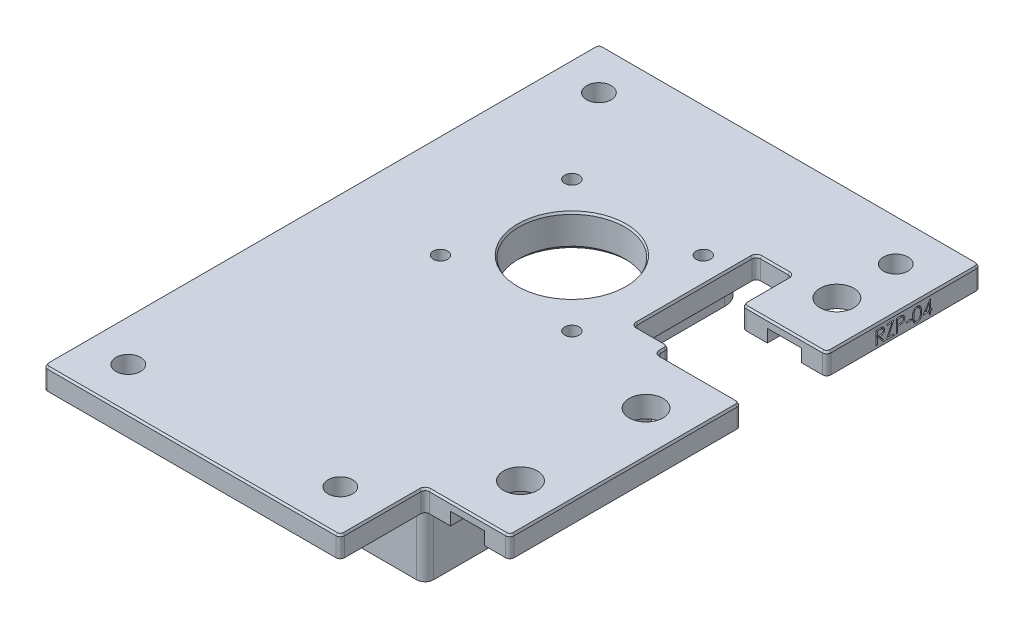
SolidWorks part; units mm, degrees
ref_plane "Front" through (0, 0, 0) normal (0, 0, 1) x (1, 0, 0)
ref_plane "Top" through (0, 0, 0) normal (0, 1, 0) x (1, 0, 0)
ref_plane "Right" through (0, 0, 0) normal (1, 0, 0) x (0, 0, -1)
sketch "Sketch1" plane through (0, 0, 0) normal (0, 1, 0) x (1, 0, 0)
  line L1 (0, 0) -> (90, 0)
  line L2 (0, 0) -> (0, 131)
  line L3 (0, 131) -> (90, 131)
  line L4 (90, 0) -> (90, 131)
  dimension "D1" = 90
  dimension "D2" = 131
extrude "Boss-Extrude1" add sketch "Sketch1" along normal blind 5
sketch "Sketch2" plane through (0, 5, 0) normal (0, 1, 0) x (1, 0, 0)
  line L0 (0, 94.625) -> (20, 94.625)
  line L1 (0, 131) -> (0, 0) construction
  line L2 (20, 94.625) -> (20, 91.625)
  line L3 (20, 91.625) -> (28.5, 91.625)
  line L4 (28.5, 91.625) -> (28.5, 77.625)
  line L5 (28.5, 77.625) -> (20, 77.625)
  line L6 (20, 77.625) -> (20, 74.625)
  line L7 (20, 74.625) -> (0, 74.625)
  line L8 (0, 74.625) -> (0, 94.625)
  line L9 (50, 84.625) -> (56.9971, 84.625) construction
  line L10 (0, 0) -> (20, 0)
  line L11 (0, 0) -> (0, 20)
  line L12 (0, 20) -> (20, 20)
  line L13 (20, 0) -> (20, 20)
  line L15 (90, 131) -> (0, 131) construction
  line L28 (28.5, 106.125) -> (28.5, 91.625) construction
  line L29 (34.5, 69.125) -> (65.5, 69.125) construction
  line L30 (34.5, 69.125) -> (34.5, 100.125) construction
  line L31 (34.5, 100.125) -> (65.5, 100.125) construction
  line L32 (65.5, 69.125) -> (65.5, 100.125) construction
  line L33 (34.5, 69.125) -> (65.5, 100.125) construction
  line L34 (34.5, 100.125) -> (65.5, 69.125) construction
  line L35 (71.5, 63.125) -> (28.5, 63.125) construction
  line L36 (71.5, 63.125) -> (71.5, 106.125) construction
  line L37 (71.5, 106.125) -> (28.5, 106.125) construction
  line L38 (28.5, 63.125) -> (28.5, 106.125) construction
  line L39 (71.5, 63.125) -> (28.5, 106.125) construction
  line L40 (71.5, 106.125) -> (28.5, 63.125) construction
  line L41 (28.5, 77.625) -> (28.5, 63.125) construction
  line L48 (32, 59.625) -> (68, 59.625) construction
  line L49 (32, 59.625) -> (32, 109.625) construction
  line L50 (32, 109.625) -> (68, 109.625) construction
  line L51 (68, 59.625) -> (68, 109.625) construction
  line L52 (32, 59.625) -> (68, 109.625) construction
  line L53 (32, 109.625) -> (68, 59.625) construction
  circle A0 centre (50, 84.625) radius 12.5
  circle A2 centre (65.5, 100.125) radius 1.7
  circle A3 centre (34.5, 100.125) radius 1.7
  circle A4 centre (65.5, 69.125) radius 1.7
  circle A5 centre (34.5, 69.125) radius 1.7
  circle A10 centre (32, 109.625) radius 1.7 construction
  circle A11 centre (68, 109.625) radius 1.7 construction
  circle A12 centre (68, 59.625) radius 1.7 construction
  circle A13 centre (32, 59.625) radius 1.7 construction
  point P14 (28.5, 84.625)
  point P54 (50, 84.625)
  dimension "D5" = 25
  dimension "D9" = 3.4
  dimension "D12" = 3.4
  dimension "D1" = 20
  dimension "D2" = 14
  dimension "D3" = 43
  dimension "D4" = 3
  dimension "D6" = 50
  dimension "D7" = 46.375
  dimension "D8" = 31
  dimension "D10" = 50
  dimension "D11" = 36
  dimension "D13" = 20
extrude "Cut-Extrude1" cut sketch "Sketch2" against normal up to next
hole_wizard "M5 Clearance Hole1" positions "Sketch3" profile "Sketch4" hole size "M5" standard "ANSI Metric" end condition through all
sketch "Sketch3" plane through (0, 5, 0) normal (0, 1, 0) x (1, 0, 0)
  line L0 (10, 20) -> (10, 131) construction
  line L1 (20, 20) -> (0, 20) construction
  line L2 (90, 131) -> (0, 131) construction
  line L5 (20, 10) -> (142.2662, 10) construction
  line L6 (20, 0) -> (20, 20) construction
  line L10 (0, 121) -> (90, 121) construction
  line L11 (0, 131) -> (0, 94.625) construction
  line L12 (90, 0) -> (90, 131) construction
  line L14 (20, 0) -> (90, 0) construction
  line L15 (0, 74.625) -> (0, 20) construction
  line L16 (90, 0) -> (90, 131) construction
  line L17 (90, 111) -> (0, 111) construction
  line L18 (90, 0) -> (90, 131) construction
  line L19 (20, 131) -> (20, 20) construction
  point P31 (10, 121)
  point P37 (80, 121)
  point P42 (30, 10)
  point P45 (80, 10)
  dimension "D1" = 10
  dimension "D2" = 10
  dimension "D3" = 10
  dimension "D4" = 10
  dimension "D5" = 10
  dimension "D6" = 10
  dimension "D7" = 20
sketch "Sketch4" plane through (80, 5, -10) normal (1, 0, 0) x (0, 0, 1)
  line L0 (0, 0) -> (0, 5)
  line L1 (0, 5) -> (2.9, 5)
  line L2 (2.9, 5) -> (2.9, 0)
  line L5 (2.9, 0) -> (0, 0)
  line L11 (0, -6.35) -> (0, 107.95) construction
  dimension "Thru Hole Dia." = 5.8
  dimension "Thru Hole Depth" = 5
sketch "Sketch6" plane through (0, 0, 0) normal (0, -1, 0) x (-1, 0, 0)
  line L0 (-20, 20) -> (0, 20) construction
  line L1 (0, 74.625) -> (-20, 74.625) construction
  line L2 (0, 74.625) -> (0, 20) construction
  line L3 (-20, 94.625) -> (0, 94.625) construction
  line L4 (0, 131) -> (0, 94.625) construction
  circle A0 centre (-10, 32.5) radius 4
  circle A1 centre (-10, 62.125) radius 4
  circle A2 centre (-10, 107.125) radius 4
  dimension "D2" = 8
  dimension "D1" = 12.5
  dimension "D3" = 12.5
  dimension "D4" = 10
  dimension "D5" = 10
  dimension "D6" = 12.5
  dimension "D7" = 10
extrude "Cut-Extrude2" cut sketch "Sketch6" against normal blind 10
other "Move Face1" flip direction yes face at (10, 2.5, -94.625) face at (10, 2.5, -74.625) offset 0.1 parameters "D1"=0.1
sketch "Sketch9" plane through (0, 0, 0) normal (0, -1, 0) x (1, 0, 0)
  line L0 (90, -111) -> (90, -20)
  line L1 (90, 0) -> (90, -131) construction
  line L2 (90, -20) -> (20, -20)
  line L3 (20, -20) -> (20, -74.525)
  line L4 (90, -111) -> (71, -111)
  line L5 (90, -131) -> (0, -131) construction
  line L6 (71, -111) -> (71, -106)
  line L7 (71, -106) -> (85, -106)
  line L8 (85, -106) -> (85, -25)
  line L9 (85, -25) -> (25, -25)
  line L10 (25, -25) -> (25, -74.525)
  line L11 (25, -74.525) -> (20, -74.525)
  line L12 (20, 0) -> (90, 0) construction
  line L13 (0, -74.525) -> (20, -74.525) construction
  line L14 (20, -74.525) -> (20, -77.625) construction
  dimension "D1" = 20
  dimension "D2" = 5
  dimension "D3" = 20
  dimension "D4" = 5
  dimension "D7" = 19
  dimension "D8" = 5
extrude "Boss-Extrude2" add sketch "Sketch9" along normal blind 15
fillet "Fillet4" radius 3 3 edges at (25, -7.5, -25) (85, -7.5, -25) (85, -7.5, -106)
fillet "Fillet5" radius 2 7 edges at (90, -7.5, -20) (90, -7.5, -111) (71, -7.5, -111) (71, -7.5, -106) (20, -7.5, -20) (25, -7.5, -74.525) (20, -7.5, -74.525)
ref_plane "Plane1" through (10, 0, 0) normal (-1, 0, 0) x (0, 0, 1)
sketch "Sketch10" plane through (10, 0, 0) normal (-1, 0, 0) x (0, 0, 1)
  line L0 (-74.525, 0) -> (-74.525, 3)
  line L1 (-28, 0) -> (-103, 0) construction
  line L2 (-74.525, 0) -> (-74.525, 5) construction
  line L3 (-74.525, 3) -> (-71.525, 0)
  line L5 (-71.525, 0) -> (-74.525, 0)
  line L6 (-97.725, 0) -> (-94.725, 0)
  line L8 (-94.725, 0) -> (-94.725, 3)
  line L10 (-94.725, 3) -> (-97.725, 0)
  line L11 (-20, 0) -> (-23, 0)
  line L13 (-20, 0) -> (0, 0) construction
  line L16 (-20, 0) -> (-20, 3)
  line L17 (-20, 0) -> (-20, 5) construction
  line L18 (-20, 3) -> (-23, 0)
  line L21 (-94.725, 0) -> (-94.725, 5) construction
  dimension "D1" = 45
  dimension "D2" = 3
extrude "Cut-Extrude5" cut sketch "Sketch10" against normal blind 4 and the other way blind 4
sketch "Sketch11" plane through (0, 5, 0) normal (0, 1, 0) x (1, 0, 0)
  line L5 (28.5, 77.625) -> (28.5, 91.625) construction
  line L6 (20, 91.625) -> (28.5, 91.625)
  line L7 (20, 91.625) -> (20, 106.625)
  line L8 (20, 106.625) -> (28.5, 106.625)
  line L9 (28.5, 91.625) -> (28.5, 106.625)
  dimension "D1" = 15
extrude "Cut-Extrude6" cut sketch "Sketch11" against normal through all
fillet "Fillet6" radius 1 14 edges at (28.5, 2.5, -77.625) (90, 2.5, 0) (90, 2.5, -131) (0, 2.5, -131) (0, 2.5, -94.725) (20, 2.5, -74.525) (20, 2.5, -77.625) (0, 2.5, -74.525) (0, 2.5, -20) (20, 2.5, 0) (20, 2.5, -20) (28.5, 2.5, -106.625) (20, 2.5, -94.725) (20, 2.5, -106.625)
sketch "Sketch15" plane through (0, 0, 0) normal (0, -1, 0) x (1, 0, 0)
  line L0 (29.5, -100.125) -> (29.5, -69.125)
  line L1 (34.5, -64.125) -> (65.5, -64.125)
  line L2 (70.5, -69.125) -> (70.5, -100.125)
  line L3 (34.5, -105.125) -> (65.5, -105.125)
  circle A0 centre (65.5, -100.125) radius 1.7 construction
  circle A1 centre (34.5, -100.125) radius 1.7 construction
  circle A2 centre (65.5, -69.125) radius 1.7 construction
  circle A3 centre (34.5, -69.125) radius 1.7 construction
  circle A4 centre (65.5, -100.125) radius 1.7
  circle A5 centre (34.5, -100.125) radius 1.7
  circle A6 centre (65.5, -69.125) radius 1.7
  circle A7 centre (34.5, -69.125) radius 1.7
  circle A8 centre (50, -84.625) radius 12.5 construction
  circle A9 centre (50, -84.625) radius 12.5
  circle A10 centre (34.5, -69.125) radius 5 construction
  circle A11 centre (34.5, -100.125) radius 5 construction
  circle A12 centre (65.5, -100.125) radius 5 construction
  circle A13 centre (65.5, -69.125) radius 5 construction
  arc A14 (29.5, -100.125) -> (34.5, -105.125) centre (34.5, -100.125) ccw
  arc A15 (29.5, -69.125) -> (34.5, -64.125) centre (34.5, -69.125) cw
  arc A16 (65.5, -64.125) -> (70.5, -69.125) centre (65.5, -69.125) cw
  arc A17 (70.5, -100.125) -> (65.5, -105.125) centre (65.5, -100.125) cw
  dimension "D1" = 10
extrude "Boss-Extrude3" add sketch "Sketch15" along normal blind 3
chamfer "Chamfer1" distance 1 angle 45 9 edges at (50, -3, -97.125) (70.5, 0, -84.625) (69.0355, 0, -65.5895) (69.0355, 0, -103.6605) (50, 0, -64.125) (50, 0, -105.125) (30.9645, 0, -65.5895) (30.9645, 0, -103.6605) (29.5, 0, -84.625)
chamfer "Printability Chamfer" distance 0.5 angle 30 29 edges at (24.25, 5, -77.625) (20.2929, 5, -77.3321) (28.2071, 5, -77.9179) (20, 5, -76.075) (28.5, 5, -92.125) (19.7071, 5, -74.8179) (28.2071, 5, -106.3321) (10, 5, -74.525) (24.25, 5, -106.625) (0.2929, 5, -74.2321) (20.2929, 5, -106.3321) (0, 5, -47.2625) (20, 5, -100.675) (0.2929, 5, -20.2929) (19.7071, 5, -95.0179) (10, 5, -20) (10, 5, -94.725) (19.7071, 5, -19.7071) (0.2929, 5, -95.0179) (20, 5, -10) (0, 5, -112.8625) (20.2929, 5, -0.2929) (0.2929, 5, -130.7071) (55, 5, 0) (45, 5, -131) (89.7071, 5, -0.2929) (89.7071, 5, -130.7071) (90, 5, -65.5) (50, 5, -72.125) first distance on face at (24.25, 2.5, -77.625) first distance on face at (20.3964, 2.5, -77.2286) first distance on face at (28.1036, 2.5, -78.0214) first distance on face at (20, 2.5, -76.075) first distance on face at (28.5, 2, -93.725) first distance on face at (19.6036, 2.5, -74.9214) first distance on face at (28.1036, 2.5, -106.2286) first distance on face at (10, 2, -74.525) first distance on face at (24.25, 2.5, -106.625) first distance on face at (0.3964, 2.5, -74.1286) first distance on face at (20.3964, 2.5, -106.2286) first distance on face at (0, 2.5, -47.2625) first distance on face at (20, 2.5, -100.675) first distance on face at (0.3964, 2.5, -20.3964) first distance on face at (19.6036, 2.5, -95.1214) first distance on face at (10, 2, -20) first distance on face at (10, 2, -94.725) first distance on face at (19.6036, 2.5, -19.6036) first distance on face at (0.3964, 2.5, -95.1214) first distance on face at (20, 2.5, -10) first distance on face at (0, 2.5, -112.8625) first distance on face at (20.3964, 2.5, -0.3964) first distance on face at (0.3964, 2.5, -130.6036) first distance on face at (55, 2.5, 0) first distance on face at (45, 2.5, -131) first distance on face at (89.6036, 2.5, -0.3964) first distance on face at (89.6036, 2.5, -130.6036) first distance on face at (90, -2.5, -65.5) first distance on face at (50, -2, -97.125)
mirror "Mirror1" about plane through (90, 5, 0) normal (-1, 0, 0) of bodies 114 108
delete or keep bodies "Body-Delete/Keep 1" type delete bodies bodies 114
sketch "Sketch12" [suppressed] plane through (0, 5, 0) normal (1, 0, 0) x (0, -1, 0)
  line L0 (4.4, 131) -> (4.4, 94.725) construction
  line L4 (5, 131) -> (0.5, 131) construction
  line L5 (5, 130) -> (5, 95.725) construction
  line L6 (0.5, 94.725) -> (5, 94.725) construction
  text T0 "LZP-04" font "Century Gothic" height in points 12
  dimension "D1" = 0.6
extrude "Left Part Num" [suppressed] cut sketch "Sketch12" along normal blind 0.4
sketch "Sketch13" plane through (180, -175, 0) normal (-1, 0, 0) x (0, 1, 0)
  line L0 (175.6, 94.725) -> (175.6, 131) construction
  line L4 (175, 131) -> (179.5, 131) construction
  line L5 (179.5, 94.725) -> (175, 94.725) construction
  line L6 (175, 130) -> (175, 95.725) construction
  text T0 "RZP-04" font "Century Gothic" height in points 12
  dimension "D1" = 0.6
extrude "Right Part Num" cut sketch "Sketch13" along normal blind 0.4
equation "\"D3@Sketch6\"=\"D1@Sketch6\""
equation "\"D6@Sketch6\"=\"D1@Sketch6\""
equation "\"D8@Sketch9\"=\"D4@Sketch9\""
equation "\"D2@Sketch9\"=\"D4@Sketch9\""
